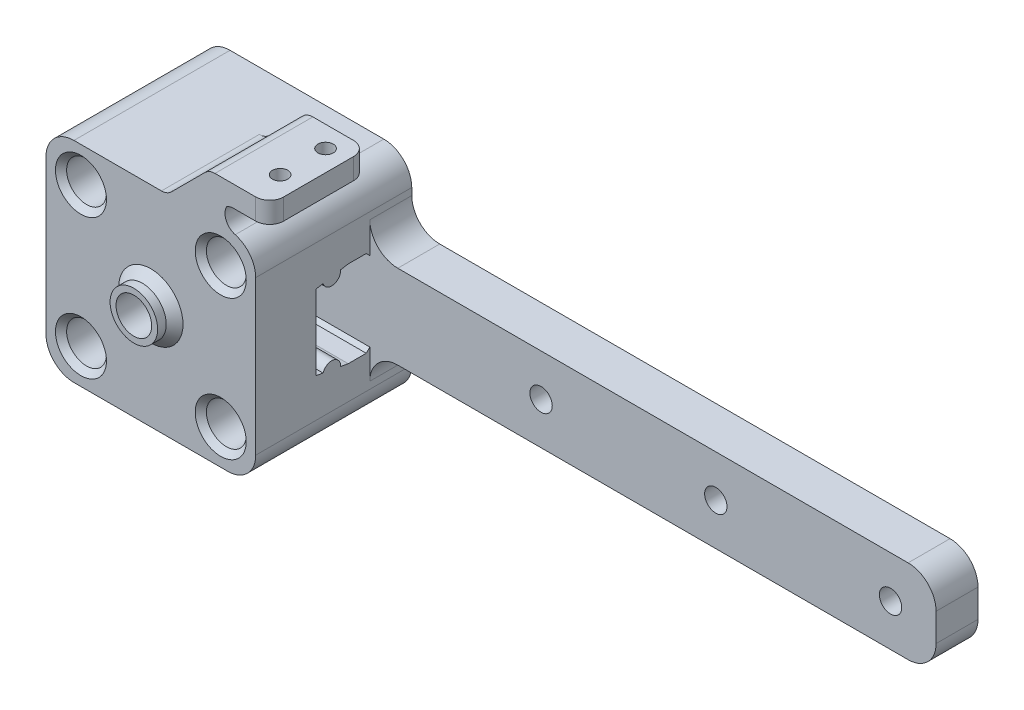
SolidWorks part; units mm, degrees
ref_plane "Front Plane" through (0, 0, 0) normal (0, 0, 1) x (1, 0, 0)
ref_plane "Top Plane" through (0, 0, 0) normal (0, 1, 0) x (1, 0, 0)
ref_plane "Right Plane" through (0, 0, 0) normal (1, 0, 0) x (0, 0, -1)
sketch "Sketch1" plane through (0, 0, 0) normal (0, 0, 1) x (1, 0, 0)
  line L0 (10, 20) -> (10, 0) construction
  line L1 (0, 0) -> (20, 0) construction
  line L2 (0, 0) -> (0, 20) construction
  line L3 (0, 20) -> (20, 20) construction
  line L4 (20, 0) -> (20, 20) construction
  line L5 (10, 10) -> (68.0208, 10) construction
  line L6 (-5, -5) -> (25, -5)
  line L7 (-5, -5) -> (-5, 25)
  line L8 (-5, 25) -> (25, 25)
  line L9 (25, -5) -> (25, 25)
  line L10 (-5, -5) -> (25, 25) construction
  line L11 (-5, 25) -> (25, -5) construction
  line L13 (25, 16) -> (106.01, 16)
  line L14 (25, 16) -> (25, 4)
  line L15 (25, 4) -> (106.01, 4)
  line L16 (106.01, 16) -> (106.01, 4)
  circle A0 centre (0, 0) radius 1.6
  circle A1 centre (0, 20) radius 1.6
  circle A2 centre (20, 20) radius 1.6
  circle A3 centre (20, 0) radius 1.6
  point P11 (10, 10)
  dimension "D2" = 3.2
  dimension "D1" = 20
  dimension "D3" = 30
  dimension "D4" = 30
  dimension "D5" = 12
  dimension "D6" = 6
  dimension "D7" = 81.01
extrude "Boss-Extrude1" add sketch "Sketch1" along normal blind 6 contours L6 L9 L8 L7 A3 A2 A1 A0 | L16 L13 L9 L15 region at (10, 10, 0) region at (65.505, 10, 0)
extrude "Boss-Extrude2" add sketch "Sketch1<3>" along normal blind 22.33 contours L6 L9 L8 L7 A3 A2 A1 A0 region at (10, 10, 0)
sketch "Sketch1<3>" plane through (0, 0, 0) normal (0, 0, 1) x (1, 0, 0) same geometry as "Sketch1"
sketch "Sketch2" plane through (25, 0, 0) normal (1, 0, 0) x (0, 0, -1)
  line L0 (-6.515, 16.0796) -> (-9.09, 16.0796)
  line L1 (-9.09, 16.0796) -> (-10.1732, 15.8886)
  line L2 (-12.69, 15.4449) -> (-13.725, 15.2624)
  line L3 (-13.725, 15.2624) -> (-13.725, 4.5369)
  line L4 (-13.725, 4.5369) -> (-12.69, 4.3544)
  line L5 (-10.1732, 3.9106) -> (-9.09, 3.7196)
  line L6 (-9.09, 3.7196) -> (-6.515, 3.7196)
  line L7 (-6.515, 3.7196) -> (-6, 4.2346)
  line L9 (-6, 15.5646) -> (-6.515, 16.0796)
  line L11 (-22.33, -5) -> (0, -5) construction
  line L12 (-22.33, -5) -> (-22.33, 25) construction
  line L13 (-6, 15.5646) -> (-6, 4.2346)
  arc A0 (-12.69, 15.4449) -> (-10.1732, 15.8886) centre (-11.459, 15.8221) ccw
  arc A1 (-10.1732, 3.9106) -> (-12.69, 4.3544) centre (-11.459, 3.9771) ccw
extrude "Cut-Extrude1" cut sketch "Sketch2" against normal through all
sketch "Sketch3" plane through (0, 0, 22.33) normal (0, 0, 1) x (1, 0, 0)
  line L0 (-5, 10) -> (25, 10) construction
  line L1 (-5, -5) -> (-5, 25) construction
  line L2 (25, -5) -> (25, 25) construction
  line L3 (10, -5) -> (10, 25) construction
  line L4 (-5, -5) -> (25, -5) construction
  line L5 (-5, 25) -> (25, 25) construction
  circle A0 centre (10, 10) radius 2.55
  dimension "D1" = 5.1
extrude "Cut-Extrude2" cut sketch "Sketch3" against normal blind 8
sketch "Sketch5" plane through (0, 0, 13.725) normal (0, 0, -1) x (-1, 0, 0)
  line L1 (-5.3235, 10) -> (-7.6617, 14.05)
  line L2 (-7.6617, 14.05) -> (-12.3383, 14.05)
  line L3 (-12.3383, 14.05) -> (-14.6765, 10)
  line L4 (-14.6765, 10) -> (-12.3383, 5.95)
  line L5 (-12.3383, 5.95) -> (-7.6617, 5.95)
  line L6 (-7.6617, 5.95) -> (-5.3235, 10)
  line L8 (-25, 15.2624) -> (-25, 4.5369)
  line L9 (-25, 4.5369) -> (5, 4.5369)
  line L10 (5, 4.5369) -> (5, 15.2624)
  line L11 (5, 15.2624) -> (-25, 15.2624)
  line L12 (-25, 15.2624) -> (-25, 4.5369)
  line L13 (-25, 4.5369) -> (5, 4.5369)
  line L15 (5, 15.2624) -> (-25, 15.2624)
  line L18 (5, 4.5369) -> (5, 15.2624)
  circle A0 centre (-10, 10) radius 4.05
  circle A1 centre (-10, 10) radius 4.05 construction
  dimension "D2" = 8.1
  dimension "D3" = 8.1
  dimension "D1" = 0
extrude "Cut-Extrude3" cut sketch "Sketch5" against normal blind 4.5 contours A0 | A0 L2 L3 | A0 L3 L4 | A0 L4 L5 | A0 L5 L6 | A0 L6 L1 | A0 L1 L2 region at (5.8141, 10, 13.725) region at (7.907, 13.6251, 13.725) region at (10, 10, 13.725) region at (7.907, 6.3749, 13.725) region at (12.093, 13.6251, 13.725) region at (12.093, 6.3749, 13.725) region at (14.1859, 10, 13.725)
sketch "Sketch6" plane through (0, 0, 0) normal (0, 0, -1) x (-1, 0, 0)
  line L0 (-20, 0) -> (0, 20) construction
  line L1 (0, 20) -> (0, 0) construction
  line L2 (0, 0) -> (-20, 20) construction
  circle A0 centre (-10, 10) radius 5
  dimension "D1" = 10
extrude "Cut-Extrude5" cut sketch "Sketch6" against normal blind 8.6
sketch "Sketch7" plane through (0, 0, 0) normal (0, 0, -1) x (-1, 0, 0)
  line L1 (5, -5) -> (-3.5, -5)
  line L2 (5, -5) -> (5, 25)
  line L3 (5, 25) -> (-3.5, 25)
  line L4 (-3.5, -5) -> (-3.5, 25)
  line L5 (5, 25) -> (-25, 25) construction
  line L6 (-106.01, 10) -> (-3.5, 10) construction
  line L7 (-106.01, 16) -> (-106.01, 4) construction
  line L8 (-3.5, 10) -> (-3.5, 16)
  line L9 (-25, 4) -> (-106.01, 4) construction
  line L10 (-3.5, 16) -> (-65, 16)
  line L11 (-3.5, 16) -> (-3.5, 4)
  line L12 (-3.5, 4) -> (-65, 4)
  line L13 (-65, 16) -> (-65, 4)
  circle A0 centre (-49.5, 10) radius 1.6
  circle A1 centre (-74.5, 10) radius 1.6
  circle A2 centre (-99.5, 10) radius 1.6
  dimension "D4" = 46
  dimension "D5" = 25
  dimension "D6" = 3.2
  dimension "D7" = 3.2
  dimension "D1" = 30
  dimension "D2" = 8.5
  dimension "D3" = 6
  dimension "D8" = 25
extrude "Cut-Extrude6" cut sketch "Sketch7" against normal through all contours L6 A2 | A2 L6 | A1 | A0 region at (99.5, 9.3209, 0) region at (99.5, 10.6791, 0)
sketch "Sketch8" plane through (0, 0, 22.33) normal (0, 0, 1) x (1, 0, 0)
  circle A0 centre (20, 20) radius 2.85
  circle A1 centre (20, 0) radius 2.85
  circle A2 centre (0, 0) radius 2.85
  circle A3 centre (0, 20) radius 2.85
  dimension "D4" = 5.7
extrude "Cut-Extrude7" cut sketch "Sketch8" against normal blind 18
sketch "Sketch9" plane through (0, 0, 22.33) normal (0, 0, 1) x (1, 0, 0)
  circle A0 centre (10, 10) radius 2.55
  circle A1 centre (10, 10) radius 3.4
  dimension "D1" = 5.1
  dimension "D2" = 6.8
extrude "Boss-Extrude3" add sketch "Sketch9" along normal blind 2.43
chamfer "Chamfer1" distance 1.2 angle 45 1 edges at (13.4, 10, 22.33)
fillet "Fillet3" radius 4 8 edges at (25, 4, 3) (25, 16, 3) (25, 25, 11.165) (-5, 25, 11.165) (-5, -5, 11.165) (25, -5, 11.165) (106.01, 4, 3) (106.01, 16, 3)
chamfer "Chamfer2" distance 0.8 angle 45 4 edges at (22.85, 0, 22.33) (2.85, 0, 22.33) (2.85, 20, 22.33) (22.85, 20, 22.33)
sketch "Sketch10" plane through (0, 0, 0) normal (0, 0, -1) x (-1, 0, 0)
  circle A0 centre (-99.5, 10) radius 2.5
  circle A1 centre (-74.5, 10) radius 2.5
  circle A2 centre (-49.5, 10) radius 2.5
  dimension "D1" = 5
extrude "Cut-Extrude8" cut sketch "Sketch10" against normal blind 3
chamfer "Chamfer3" distance 0.8 angle 45 3 edges at (47, 10, 0) (97, 10, 0) (72, 10, 0)
sketch "Sketch15" plane through (0, 0, 22.33) normal (0, 0, 1) x (1, 0, 0)
  line L0 (12.3431, 25) -> (18.3431, 31)
  line L1 (18.3431, 31) -> (27, 31)
  line L2 (27, 31) -> (27, 28)
  line L3 (27, 28) -> (21, 28)
  line L4 (25, -1) -> (25, 21)
  line L5 (21, 25) -> (-1, 25)
  line L6 (-5, 21) -> (-5, -1)
  line L7 (-1, -5) -> (21, -5)
  line L8 (25, -1) -> (25, 21)
  line L9 (21, 25) -> (-1, 25)
  line L10 (-5, 21) -> (-5, -1)
  line L11 (-1, -5) -> (21, -5)
  line L12 (21, 28) -> (18, 25)
  arc A4 (25, 21) -> (21, 25) centre (21, 21) ccw
  arc A5 (-1, 25) -> (-5, 21) centre (-1, 21) ccw
  arc A6 (-5, -1) -> (-1, -5) centre (-1, -1) ccw
  arc A7 (21, -5) -> (25, -1) centre (21, -1) ccw
  arc A8 (25, 21) -> (21, 25) centre (21, 21) ccw
  arc A9 (-1, 25) -> (-5, 21) centre (-1, 21) ccw
  arc A10 (-5, -1) -> (-1, -5) centre (-1, -1) ccw
  arc A11 (21, -5) -> (25, -1) centre (21, -1) ccw
  dimension "D2" = 3
  dimension "D3" = 3
  dimension "D4" = 4
  dimension "D5" = 3
  dimension "D6" = 45
  dimension "D7" = 6
  dimension "D1" = 0
extrude "Boss-Extrude6" add sketch "Sketch15" against normal blind 14 contours L12 L3 L2 L1 L0 L9 region at (20.0198, 28.3794, 22.33)
sketch "Sketch17" plane through (0, 31, 0) normal (0, 1, 0) x (1, 0, 0)
  line L0 (27, -8.33) -> (27, -22.33) construction
  line L1 (18.3431, -8.33) -> (27, -8.33) construction
  circle A0 centre (24, -11.33) radius 1.1
  circle A1 centre (24, -17.83) radius 1.1
  dimension "D1" = 2.2
  dimension "D2" = 6.5
  dimension "D3" = 3
  dimension "D4" = 3
  dimension "D5" = 3
extrude "Cut-Extrude10" cut sketch "Sketch17" against normal up to next
fillet "Fillet5" radius 2 6 edges at (21, 28, 15.33) (27, 29.5, 22.33) (27, 29.5, 8.33) (18.3431, 31, 15.33) (12.3431, 25, 15.33) (18, 25, 15.33)
